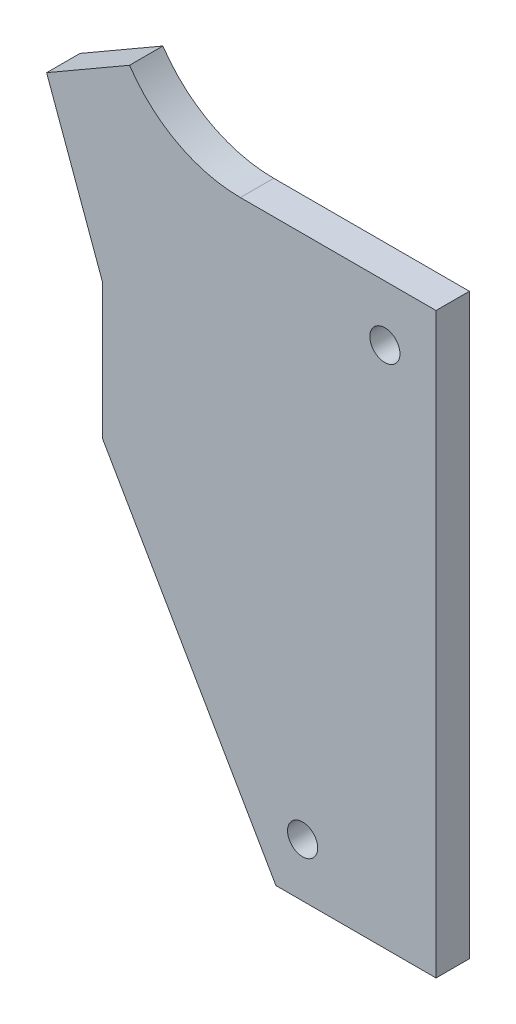
SolidWorks part; units mm, degrees
ref_plane "Front Plane" through (0, 0, 0) normal (0, 0, 1) x (1, 0, 0)
ref_plane "Top Plane" through (0, 0, 0) normal (0, 1, 0) x (1, 0, 0)
ref_plane "Right Plane" through (0, 0, 0) normal (1, 0, 0) x (0, 0, -1)
sketch "Sketch1" plane through (0, 0, 0) normal (0, 0, 1) x (1, 0, 0)
  line L7 (-3103.6988, 1002.3457) -> (-3103.6988, 1084.8957)
  line L8 (-3103.6988, 1084.8957) -> (-3131.6388, 1084.8957)
  line L9 (-3147.4648, 1093.342) -> (-3159.3056, 1086.5057)
  line L10 (-3159.3056, 1086.5057) -> (-3151.3238, 1064.5757)
  line L11 (-3151.3238, 1064.5757) -> (-3151.3238, 1045.2399)
  line L12 (-3151.3238, 1045.2399) -> (-3126.5588, 1002.3457)
  line L13 (-3126.5588, 1002.3457) -> (-3103.6988, 1002.3457)
  line L14 (-3103.6988, 1002.3457) -> (-3103.6988, 1084.8957)
  line L15 (-3103.6988, 1084.8957) -> (-3131.6388, 1084.8957)
  line L16 (-3147.4648, 1093.342) -> (-3159.3056, 1086.5057)
  line L17 (-3159.3056, 1086.5057) -> (-3151.3238, 1064.5757)
  line L18 (-3151.3238, 1064.5757) -> (-3151.3238, 1045.2399)
  line L19 (-3151.3238, 1045.2399) -> (-3126.5588, 1002.3457)
  line L20 (-3126.5588, 1002.3457) -> (-3103.6988, 1002.3457)
  arc A1 (-3147.4648, 1093.342) -> (-3131.6388, 1084.8957) centre (-3131.6388, 1103.9457) ccw
  arc A2 (-3147.4648, 1093.342) -> (-3131.6388, 1084.8957) centre (-3131.6388, 1103.9457) ccw
  dimension "D1" = 0
extrude "Boss-Extrude1" add sketch "Sketch1" along normal blind 4.7625
hole_wizard "#6 Clearance Hole1" positions "Sketch3" profile "Sketch2" hole size "#6" standard "ANSI Inch" end condition through all
sketch "Sketch3" plane through (0, 0, 4.7625) normal (0, 0, 1) x (1, 0, 0)
  point P0 (-3122.7488, 1009.9657)
  point P3 (-3111.0013, 1076.9582)
sketch "Sketch2" plane through (-3122.7488, 1009.9657, 4.7625) normal (1, 0, 0) x (0, -1, 0)
  line L0 (0, 0) -> (0, 4.7625)
  line L1 (0, 4.7625) -> (2.1526, 4.7625)
  line L2 (2.1526, 4.7625) -> (2.1526, 0)
  line L5 (2.1526, 0) -> (0, 0)
  line L11 (0, -6.35) -> (0, 107.95) construction
  dimension "Thru Hole Dia." = 4.3053
  dimension "Thru Hole Depth" = 4.7625
